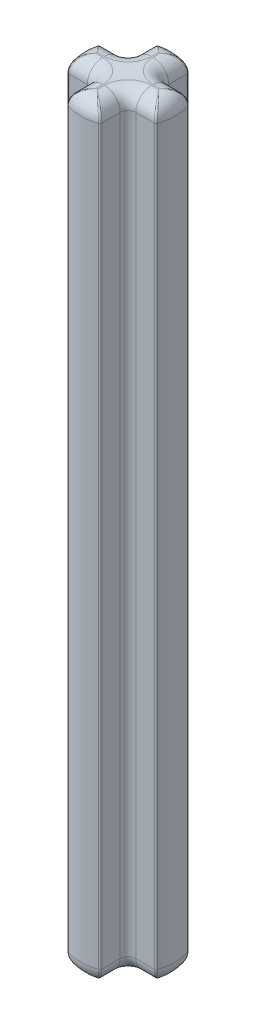
SolidWorks part; units mm, degrees
ref_plane "Front Plane" through (0, 0, 0) normal (0, 0, 1) x (1, 0, 0)
ref_plane "Top Plane" through (0, 0, 0) normal (0, 1, 0) x (1, 0, 0)
ref_plane "Right Plane" through (0, 0, 0) normal (1, 0, 0) x (0, 0, -1)
sketch "Sketch1" plane through (0, 0, 0) normal (0, 1, 0) x (1, 0, 0)
  line L0 (1.24, -0.84) -> (2.1777, -0.84)
  line L2 (-0.84, 2.1777) -> (-0.84, 1.24)
  line L4 (0.84, 2.1777) -> (0.84, 1.24)
  line L5 (-0.84, 2.2482) -> (0.84, -2.2482) construction
  line L6 (-0.84, -2.2482) -> (0.84, 2.2482) construction
  line L7 (-2.1777, 0.84) -> (-1.24, 0.84)
  line L9 (-2.1777, -0.84) -> (-1.24, -0.84)
  line L11 (-2.2482, 0.84) -> (2.2482, -0.84) construction
  line L12 (-2.2482, -0.84) -> (2.2482, 0.84) construction
  line L13 (0.84, -1.24) -> (0.84, -2.1777)
  line L14 (1.24, 0.84) -> (2.1777, 0.84)
  line L15 (-0.84, -1.24) -> (-0.84, -2.1777)
  arc A0 (-2.2724, 0.7722) -> (-2.2724, -0.7722) centre (0, 0) ccw
  arc A1 (0.7722, 2.2724) -> (-0.7722, 2.2724) centre (0, 0) ccw
  arc A2 (2.2724, -0.7722) -> (2.2724, 0.7722) centre (0, 0) ccw
  arc A3 (-0.7722, -2.2724) -> (0.7722, -2.2724) centre (0, 0) ccw
  arc A4 (0.7722, -2.2724) -> (0.84, -2.1777) centre (0.74, -2.1777) ccw
  arc A5 (-0.84, -2.1777) -> (-0.7722, -2.2724) centre (-0.74, -2.1777) ccw
  arc A6 (-2.1777, 0.84) -> (-2.2724, 0.7722) centre (-2.1777, 0.74) ccw
  arc A7 (-2.2724, -0.7722) -> (-2.1777, -0.84) centre (-2.1777, -0.74) ccw
  arc A8 (2.1777, -0.84) -> (2.2724, -0.7722) centre (2.1777, -0.74) ccw
  arc A9 (2.1777, 0.84) -> (2.2724, 0.7722) centre (2.1777, 0.74) cw
  arc A10 (0.7722, 2.2724) -> (0.84, 2.1777) centre (0.74, 2.1777) cw
  arc A11 (-0.7722, 2.2724) -> (-0.84, 2.1777) centre (-0.74, 2.1777) ccw
  arc A12 (-1.24, -0.84) -> (-0.84, -1.24) centre (-1.24, -1.24) cw
  arc A13 (1.24, -0.84) -> (0.84, -1.24) centre (1.24, -1.24) ccw
  arc A14 (1.24, 0.84) -> (0.84, 1.24) centre (1.24, 1.24) cw
  arc A15 (-1.24, 0.84) -> (-0.84, 1.24) centre (-1.24, 1.24) ccw
  point P40 (-0.84, -0.84)
  point P43 (0.84, -0.84)
  dimension "D1" = 4.8
  dimension "D3" = 0.1
  dimension "D4" = 0.4
  dimension "D2" = 1.68
extrude "Boss-Extrude1" add sketch "Sketch1" along normal blind 39
fillet "Fillet1" radius 0.8 24 edges at (0.8213, 39, -2.2359) (0.84, 39, -1.7089) (0.9572, 39, -0.9572) (1.7089, 39, -0.84) (2.2359, 39, -0.8213) (2.4, 39, 0) (2.2359, 39, 0.8213) (1.7089, 39, 0.84) (0.9572, 39, 0.9572) (0.84, 39, 1.7089) (0.8213, 39, 2.2359) (0, 39, 2.4) (-0.8213, 39, 2.2359) (-0.84, 39, 1.7089) (-0.9572, 39, 0.9572) (-1.7089, 39, 0.84) (-2.2359, 39, 0.8213) (-2.4, 39, 0) (-2.2359, 39, -0.8213) (-1.7089, 39, -0.84) (-0.9572, 39, -0.9572) (-0.84, 39, -1.7089) (-0.8213, 39, -2.2359) (0, 39, -2.4)
fillet "Fillet2" radius 0.8 24 edges at (0.8213, 0, -2.2359) (0.84, 0, -1.7089) (0.9572, 0, -0.9572) (1.7089, 0, -0.84) (2.2359, 0, -0.8213) (2.4, 0, 0) (2.2359, 0, 0.8213) (1.7089, 0, 0.84) (0.9572, 0, 0.9572) (0.84, 0, 1.7089) (0.8213, 0, 2.2359) (0, 0, 2.4) (-0.8213, 0, 2.2359) (-0.84, 0, 1.7089) (-0.9572, 0, 0.9572) (-1.7089, 0, 0.84) (-2.2359, 0, 0.8213) (-2.4, 0, 0) (-2.2359, 0, -0.8213) (-1.7089, 0, -0.84) (-0.9572, 0, -0.9572) (-0.84, 0, -1.7089) (-0.8213, 0, -2.2359) (0, 0, -2.4)
